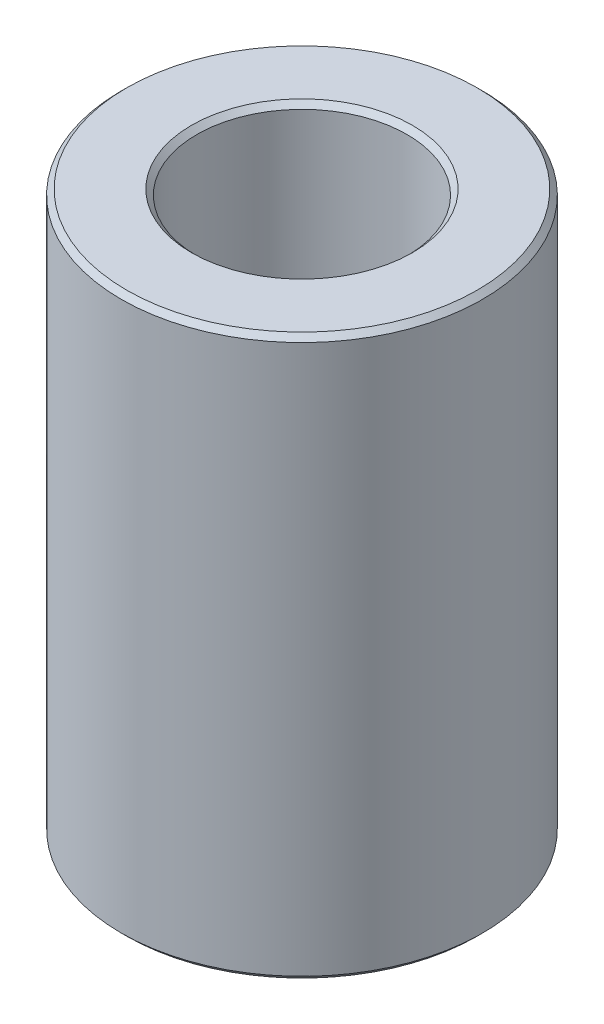
SolidWorks part; units mm, degrees
ref_plane "Front Plane" through (0, 0, 0) normal (0, 0, 1) x (1, 0, 0)
ref_plane "Top Plane" through (0, 0, 0) normal (0, 1, 0) x (1, 0, 0)
ref_plane "Right Plane" through (0, 0, 0) normal (1, 0, 0) x (0, 0, -1)
sketch "Sketch1" plane through (0, 0, 0) normal (0, 1, 0) x (1, 0, 0)
  circle A0 centre (0, 0) radius 25
  dimension "SLEEVE_OD" = 50
extrude "Boss-Extrude1" add sketch "Sketch1" along normal blind 77.4478
sketch "Sketch2" plane through (0, 0, 0) normal (0, 1, 0) x (1, 0, 0)
  circle A0 centre (0, 0) radius 14.5491
  dimension "BORE_D" = 29.0981
extrude "Cut-Extrude1" cut sketch "Sketch2" along normal through all
chamfer "Chamfer1" distance 0.7371 angle 45 4 edges at (0, 77.4478, 14.5491) (0, 0, 14.5491) (0, 0, 25) (0, 77.4478, 25)
